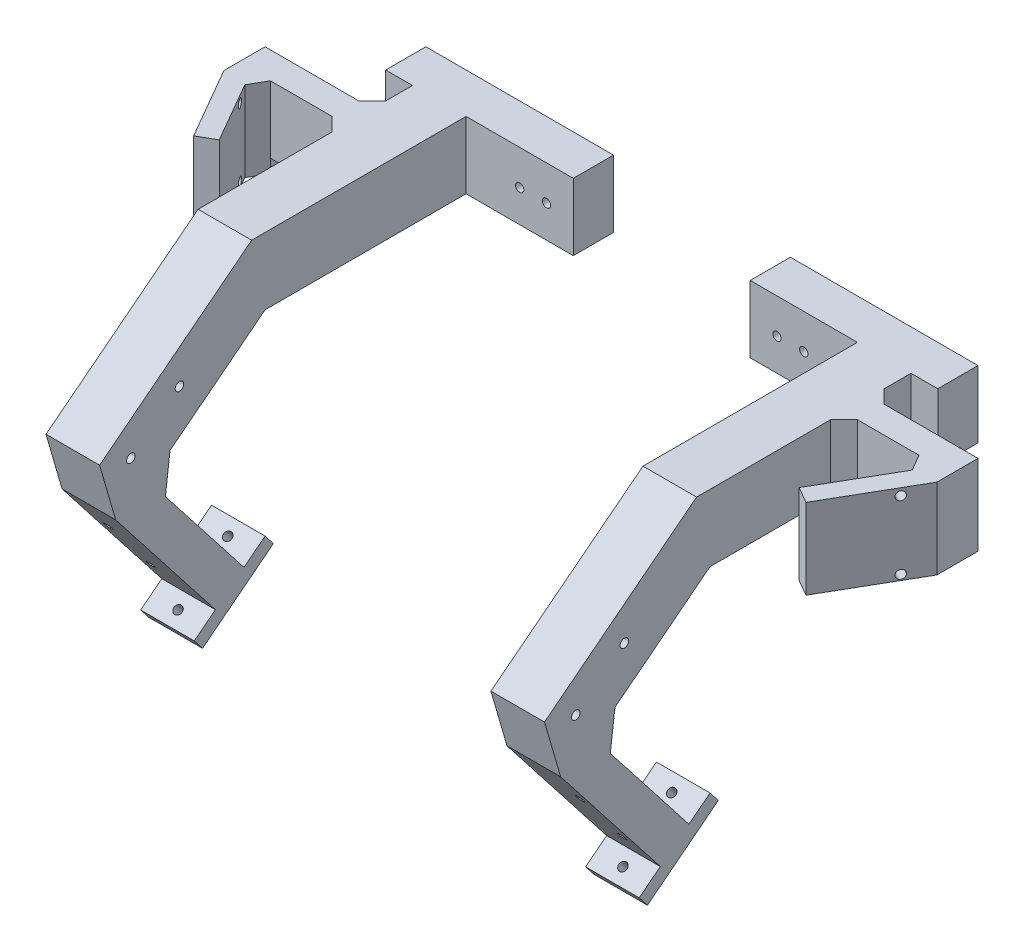
SolidWorks part; units mm, degrees
ref_plane "前视基准面" through (0, 0, 0) normal (0, 0, 1) x (1, 0, 0)
ref_plane "上视基准面" through (0, 0, 0) normal (0, 1, 0) x (1, 0, 0)
ref_plane "右视基准面" through (0, 0, 0) normal (1, 0, 0) x (0, 0, -1)
other "Configuration Table"
sketch "草图1" plane through (0, 0, 0) normal (0, 0, 1) x (1, 0, 0)
  line L1 (-103, 12.5) -> (103, 12.5)
  line L2 (-103, 12.5) -> (-103, -12.5)
  line L3 (-103, -12.5) -> (103, -12.5)
  line L4 (103, 12.5) -> (103, -12.5)
  line L5 (0, -12.5) -> (0, 12.5) construction
  line L6 (-103, 0) -> (103, 0) construction
  point P0 (0, 0)
  dimension "D1" = 25
  dimension "D2" = 206
extrude "凸台-拉伸1" add sketch "草图1" along normal blind 15
sketch "草图3" plane through (103, 0, 0) normal (1, 0, 0) x (0, 0, -1)
  line L2 (-90, -12.5) -> (-133.3406, -46.3614)
  line L6 (-15, 12.5) -> (-15, -12.5)
  line L7 (-15, 12.5) -> (-95, 12.5)
  line L8 (-15, -12.5) -> (-90, -12.5)
  line L13 (-95, 12.5) -> (-158.0409, -36.7529)
  line L14 (-115.7557, -160.3241) -> (-65.323, -120.9218) construction
  line L15 (-158.0409, -36.7529) -> (-133.3406, -46.3614)
  dimension "D1" = 80
  dimension "D2" = 75
  dimension "D3" = 80
  dimension "D4" = 55
extrude "凸台-拉伸2" add sketch "草图3" against normal blind 30
sketch "草图4" plane through (-103, 0, 0) normal (-1, 0, 0) x (0, 0, 1)
  line L6 (15, 12.5) -> (15, -12.5)
  line L7 (15, -12.5) -> (90, -12.5)
  line L8 (90, -12.5) -> (133.3406, -46.3614)
  line L9 (90, -12.5) -> (133.3406, -46.3614)
  line L10 (133.3406, -46.3614) -> (158.0409, -36.7529)
  line L11 (95, 12.5) -> (15, 12.5)
  line L12 (15, 12.5) -> (15, -12.5)
  line L13 (15, -12.5) -> (90, -12.5)
  line L17 (95, 12.5) -> (15, 12.5)
  line L18 (133.3406, -46.3614) -> (158.0409, -36.7529)
  line L19 (158.0409, -36.7529) -> (95, 12.5)
  line L20 (158.0409, -36.7529) -> (95, 12.5)
  dimension "D1" = 0
extrude "凸台-拉伸3" add sketch "草图4" against normal blind 30
extrude "切除-拉伸1" cut sketch "草图3<2>" against normal blind 10
sketch "草图3<2>" plane through (103, 0, 0) normal (1, 0, 0) x (0, 0, -1) same geometry as "草图3"
extrude "切除-拉伸2" cut sketch "草图4<2>" against normal blind 10
sketch "草图4<2>" plane through (-103, 0, 0) normal (-1, 0, 0) x (0, 0, 1) same geometry as "草图4"
sketch "草图12" plane through (0, 0, 15) normal (0, 0, 1) x (1, 0, 0)
  line L1 (73, 12.5) -> (-73, 12.5) construction
  line L2 (-73, 12.5) -> (-73, -12.5) construction
  circle A0 centre (-53, -0.5) radius 1.55
  circle A1 centre (-43, -0.5) radius 1.55
  dimension "D1" = 3.1
  dimension "D4" = 3.1
  dimension "D2" = 20
  dimension "D3" = 13
extrude "切除-拉伸6" cut sketch "草图12" against normal through all
sketch "草图13" plane through (-93, 0, 0) normal (-1, 0, 0) x (0, 0, 1)
  line L0 (133.3406, -46.3614) -> (94.7816, -95.7147)
  line L2 (158.0409, -36.7529) -> (105.4579, -104.056)
  line L3 (158.0409, -36.7529) -> (133.3406, -46.3614)
  line L4 (94.7816, -95.7147) -> (105.4579, -104.056)
extrude "凸台-拉伸5" add sketch "草图13" along direction (-1, 0, 0) on the side against the normal blind 20
sketch "草图14" plane through (93, 0, 0) normal (1, 0, 0) x (0, 0, -1)
  line L4 (-94.7816, -95.7147) -> (-133.3406, -46.3614)
  line L5 (-105.4579, -104.056) -> (-94.7816, -95.7147)
  line L6 (-158.0409, -36.7529) -> (-105.4579, -104.056)
  line L7 (-133.3406, -46.3614) -> (-158.0409, -36.7529)
  line L8 (-94.7816, -95.7147) -> (-133.3406, -46.3614)
  line L9 (-105.4579, -104.056) -> (-94.7816, -95.7147)
  line L10 (-158.0409, -36.7529) -> (-105.4579, -104.056)
  line L11 (-133.3406, -46.3614) -> (-158.0409, -36.7529)
  dimension "D1" = 0
extrude "凸台-拉伸6" add sketch "草图14" against normal blind 20
sketch "草图15" plane through (-93, 0, 0) normal (-1, 0, 0) x (0, 0, 1)
  line L0 (97.8599, -91.7746) -> (89.9798, -85.618)
  line L1 (133.3406, -46.3614) -> (94.7816, -95.7147) construction
  line L2 (97.8599, -91.7746) -> (94.7816, -95.7147)
  line L3 (89.9798, -85.618) -> (86.9015, -89.5581)
  line L5 (86.9015, -89.5581) -> (94.7816, -95.7147)
  line L6 (108.5363, -100.1159) -> (116.4164, -106.2725)
  line L7 (105.4579, -104.056) -> (158.0409, -36.7529) construction
  line L8 (116.4164, -106.2725) -> (113.3381, -110.2126)
  line L9 (113.3381, -110.2126) -> (105.4579, -104.056)
  line L10 (105.4579, -104.056) -> (108.5363, -100.1159)
  dimension "D1" = 10
  dimension "D2" = 5
  dimension "D3" = 10
  dimension "D4" = 5
extrude "凸台-拉伸7" add sketch "草图15" against normal blind 20
sketch "草图16" plane through (93, 0, 0) normal (1, 0, 0) x (0, 0, -1)
  line L4 (-108.5363, -100.1159) -> (-116.4164, -106.2725)
  line L5 (-116.4164, -106.2725) -> (-113.3381, -110.2126)
  line L6 (-113.3381, -110.2126) -> (-105.4579, -104.056)
  line L7 (-105.4579, -104.056) -> (-108.5363, -100.1159)
  line L8 (-108.5363, -100.1159) -> (-116.4164, -106.2725)
  line L9 (-116.4164, -106.2725) -> (-113.3381, -110.2126)
  line L10 (-113.3381, -110.2126) -> (-105.4579, -104.056)
  line L11 (-105.4579, -104.056) -> (-108.5363, -100.1159)
  line L12 (-89.9798, -85.618) -> (-97.8599, -91.7746)
  line L13 (-86.9015, -89.5581) -> (-89.9798, -85.618)
  line L14 (-94.7816, -95.7147) -> (-86.9015, -89.5581)
  line L15 (-97.8599, -91.7746) -> (-94.7816, -95.7147)
  line L16 (-89.9798, -85.618) -> (-97.8599, -91.7746)
  line L17 (-86.9015, -89.5581) -> (-89.9798, -85.618)
  line L18 (-94.7816, -95.7147) -> (-86.9015, -89.5581)
  line L19 (-97.8599, -91.7746) -> (-94.7816, -95.7147)
  dimension "D1" = 0
  dimension "D2" = 0
extrude "凸台-拉伸8" add sketch "草图16" against normal blind 20
sketch "草图17" plane through (0, -9.5119, -7.4315) normal (0, 0.788, 0.6157) x (1, 0, 0)
  circle A0 centre (-83, -152.1653) radius 1.55
  circle A1 centre (-83, -128.6167) radius 1.55
  dimension "D1" = 3.1
  dimension "D2" = 3.1
extrude "切除-拉伸7" cut sketch "草图17" against normal blind 20
sketch "草图20" plane through (0, -9.5119, -7.4315) normal (0, 0.788, 0.6157) x (1, 0, 0)
  circle A0 centre (83, -152.1653) radius 1.55
  circle A1 centre (82.648, -128.6167) radius 1.55
  dimension "D1" = 3.1
  dimension "D2" = 3.1
extrude "切除-拉伸8" cut sketch "草图20" against normal blind 20
sketch "草图21" plane through (0, 0, 0) normal (0, 0, -1) x (-1, 0, 0)
  circle A0 centre (-43, -0.5) radius 1.55
  circle A1 centre (-53, -0.5) radius 1.55
extrude "切除-拉伸9" cut sketch "草图21" against normal blind 20
sketch "草图22" plane through (73, 0, 0) normal (-1, 0, 0) x (0, 0, 1)
  circle A0 centre (140.0641, -35.3981) radius 1.6
  circle A1 centre (121.9398, -21.2379) radius 1.6
extrude "切除-拉伸10" cut sketch "草图22" against normal through all
sketch "草图23" plane through (-73, 0, 0) normal (1, 0, 0) x (0, 0, -1)
  circle A0 centre (-121.9398, -21.2379) radius 1.6
  circle A1 centre (-140.0641, -35.3981) radius 1.6
extrude "切除-拉伸11" cut sketch "草图23" against normal through all
sketch "草图24" plane through (0, -90.604, 115.9678) normal (0, -0.6157, 0.788) x (1, 0, 0)
  line L0 (93, 68.338) -> (93, -12.0708) construction
  line L1 (73, -12.0708) -> (93, -12.0708) construction
  circle A0 centre (88, 28.3292) radius 1.55
  circle A1 centre (88, 2.9292) radius 1.55
  dimension "D3" = 3.1
  dimension "D4" = 3.1
  dimension "D1" = 5
  dimension "D2" = 5
  dimension "D5" = 25.4
  dimension "D6" = 15
extrude "切除-拉伸12" cut sketch "草图24" against normal up to next
sketch "草图25" plane through (0, -90.604, 115.9678) normal (0, -0.6157, 0.788) x (1, 0, 0)
  line L0 (-93, -12.0708) -> (-93, 68.338) construction
  line L1 (-93, 19.0851) -> (-93, -0.6152) construction
  line L2 (-73, -12.0708) -> (-93, -12.0708) construction
  circle A0 centre (-88, 28.3292) radius 1.55
  circle A1 centre (-88, 2.9292) radius 1.55
  dimension "D2" = 3.1
  dimension "D3" = 3.1
  dimension "D1" = 25.4
  dimension "D4" = 5
  dimension "D5" = 5
  dimension "D6" = 15
extrude "切除-拉伸13" cut sketch "草图25" against normal up to next
sketch "草图26" plane through (0, 12.5, 0) normal (0, 1, 0) x (1, 0, 0)
  line L0 (-93, -30) -> (-93, -40)
  line L1 (-93, -95) -> (-93, -15) construction
  line L2 (-93, -40) -> (-128, -40)
  line L3 (-133, -45.3397) -> (-133, -30)
  line L4 (-133, -30) -> (-93, -30)
  line L5 (-128, -40) -> (-111.478, -68.617)
  line L6 (-111.478, -68.617) -> (-117.5401, -72.117)
  line L7 (-117.5401, -72.117) -> (-133, -45.3397)
  line L8 (-93, -15) -> (-103, -15) construction
  dimension "D1" = 15
  dimension "D2" = 10
  dimension "D3" = 60
  dimension "D4" = 40
  dimension "D5" = 35
  dimension "D7" = 7
extrude "凸台-拉伸9" add sketch "草图26" along direction (0, 1, 0) on the side against the normal blind 25
sketch "草图27" plane through (0, -12.5, 0) normal (0, -1, 0) x (1, 0, 0)
  line L0 (93, 30) -> (133, 30)
  line L1 (93, 90) -> (93, 15) construction
  line L2 (133, 30) -> (133, 45.3397)
  line L3 (128, 40) -> (93, 40)
  line L4 (93, 40) -> (93, 30)
  line L5 (133, 45.3397) -> (115.124, 76.3019)
  line L6 (115.124, 76.3019) -> (109.0618, 72.8019)
  line L7 (109.0618, 72.8019) -> (128, 40)
  line L8 (93, 15) -> (103, 15) construction
  dimension "D1" = 7
  dimension "D2" = 40
  dimension "D3" = 15
  dimension "D5" = 35
  dimension "D6" = 60
  dimension "D8" = 10
extrude "凸台-拉伸10" add sketch "草图27" against normal blind 25
sketch "草图28" plane through (0, 12.5, 0) normal (0, 1, 0) x (1, 0, 0)
  line L0 (-124.5, -46.0622) -> (-121, -40)
  line L1 (-111.478, -68.617) -> (-128, -40) construction
  line L2 (-128, -40) -> (-93, -40) construction
  line L3 (-121, -40) -> (-128, -40)
  line L4 (-128, -40) -> (-124.5, -46.0622)
  line L5 (121, -40) -> (128, -40)
  line L6 (128, -40) -> (93, -40) construction
  line L7 (128, -40) -> (124.5, -46.0622)
  line L8 (109.0618, -72.8019) -> (128, -40) construction
  line L9 (124.5, -46.0622) -> (121, -40)
  dimension "D1" = 7
  dimension "D2" = 7
  dimension "D3" = 7
  dimension "D4" = 7
extrude "凸台-拉伸11" add sketch "草图28" against normal blind 25
sketch "草图29" plane through (0, 12.5, 0) normal (0, 1, 0) x (1, 0, 0)
  line L0 (-124.5, -46.0622) -> (-111.478, -68.617)
  line L1 (-111.478, -68.617) -> (-117.5401, -72.117)
  line L2 (-117.5401, -72.117) -> (-133, -45.3397)
  line L3 (-133, -45.3397) -> (-117.5401, -72.117) construction
  line L4 (-133, -45.3397) -> (-133, -30)
  line L5 (-133, -30) -> (-121, -30)
  line L6 (-93, -30) -> (-133, -30) construction
  line L7 (-121, -30) -> (-121, -40)
  line L8 (-121, -40) -> (-124.5, -46.0622)
  line L9 (109.0618, -72.8019) -> (115.124, -76.3019)
  line L10 (115.124, -76.3019) -> (133, -45.3397)
  line L11 (133, -45.3397) -> (133, -30)
  line L12 (109.0618, -72.8019) -> (124.5, -46.0622)
  line L13 (124.5, -46.0622) -> (121, -40)
  line L14 (121, -40) -> (121, -30)
  line L15 (93, -30) -> (133, -30) construction
  line L16 (121, -30) -> (133, -30)
sketch "草图30" plane through (0, -12.5, 0) normal (0, -1, 0) x (1, 0, 0)
  line L7 (-124.5, 46.0622) -> (-111.478, 68.617)
  line L8 (-111.478, 68.617) -> (-117.5401, 72.117)
  line L9 (-117.5401, 72.117) -> (-133, 45.3397)
  line L10 (-133, 45.3397) -> (-133, 30)
  line L11 (-133, 30) -> (-121, 30)
  line L12 (-121, 30) -> (-121, 40)
  line L13 (-121, 40) -> (-124.5, 46.0622)
  line L14 (-124.5, 46.0622) -> (-111.478, 68.617)
  line L15 (-111.478, 68.617) -> (-117.5401, 72.117)
  line L16 (-117.5401, 72.117) -> (-133, 45.3397)
  line L17 (-133, 45.3397) -> (-133, 30)
  line L18 (-133, 30) -> (-121, 30)
  line L19 (-121, 30) -> (-121, 40)
  line L20 (-121, 40) -> (-124.5, 46.0622)
  line L21 (133, 45.3397) -> (115.124, 76.3019)
  line L22 (133, 30) -> (133, 45.3397)
  line L23 (121, 30) -> (133, 30)
  line L24 (121, 40) -> (121, 30)
  line L25 (124.5, 46.0622) -> (121, 40)
  line L26 (109.0618, 72.8019) -> (124.5, 46.0622)
  line L27 (115.124, 76.3019) -> (109.0618, 72.8019)
  line L28 (133, 45.3397) -> (115.124, 76.3019)
  line L29 (133, 30) -> (133, 45.3397)
  line L30 (121, 30) -> (133, 30)
  line L31 (121, 40) -> (121, 30)
  line L32 (124.5, 46.0622) -> (121, 40)
  line L33 (109.0618, 72.8019) -> (124.5, 46.0622)
  line L34 (115.124, 76.3019) -> (109.0618, 72.8019)
  dimension "D1" = 0
  dimension "D2" = 0
extrude "凸台-拉伸13" add sketch "草图30" along normal blind 5
sketch "草图31" plane through (119.3827, 0, 68.9256) normal (0.866, 0, 0.5) x (0.5, 0, -0.866)
  line L1 (27.2346, -17.5) -> (-8.5174, -17.5) construction
  circle A0 centre (17.359, 9.9) radius 1.6
  circle A1 centre (17.359, -15.5) radius 1.6
  dimension "D5" = 3.2
  dimension "D6" = 3.2
  dimension "D2" = 0
  dimension "D3" = 25.4
  dimension "D4" = 2
extrude "切除-拉伸14" cut sketch "草图31" against normal up to next and the other way through all
sketch "草图33" plane through (-119.3827, 0, 68.9256) normal (-0.866, 0, 0.5) x (0.5, 0, 0.866)
  line L0 (3.6851, -17.5) -> (-27.2346, -17.5) construction
  circle A0 centre (-17.359, 9.9) radius 1.6
  circle A1 centre (-17.359, -15.5) radius 1.6
  dimension "D5" = 3.2
  dimension "D6" = 3.2
  dimension "D2" = 25.4
  dimension "D3" = 2
  dimension "D4" = 0
extrude "切除-拉伸15" cut sketch "草图33" against normal up to next
sketch "草图34" plane through (0, 12.5, 0) normal (0, 1, 0) x (1, 0, 0)
  line L0 (-98, -40) -> (-93, -45)
  line L1 (-121, -40) -> (-93, -40) construction
  line L2 (-93, -95) -> (-93, -40) construction
  line L3 (-93, -40) -> (-93, -45)
  line L4 (-98, -40) -> (-93, -40)
  line L5 (-98, -30) -> (-93, -25)
  line L6 (-93, -30) -> (-133, -30) construction
  line L7 (-93, -30) -> (-93, -15) construction
  line L8 (-93, -25) -> (-93, -30)
  line L9 (-93, -30) -> (-98, -30)
  line L20 (93, -25) -> (93, -30)
  line L21 (93, -15) -> (93, -30) construction
  line L22 (93, -30) -> (98, -30)
  line L23 (93, -30) -> (133, -30) construction
  line L24 (98, -30) -> (93, -25)
  line L25 (93, -45) -> (93, -40)
  line L26 (93, -40) -> (93, -95) construction
  line L27 (93, -40) -> (98, -40)
  line L28 (98, -40) -> (93, -45)
  dimension "D1" = 5
  dimension "D2" = 5
  dimension "D3" = 5
  dimension "D4" = 5
  dimension "D5" = 5
  dimension "D6" = 5
  dimension "D7" = 5
extrude "凸台-拉伸14" add sketch "草图34" along direction (0, 1, 0) on the side against the normal blind 25
sketch "草图35" plane through (-93, 0, 0) normal (-1, 0, 0) x (0, 0, 1)
  line L0 (125.4605, -40.2048) -> (133.3406, -46.3614)
  line L1 (90, -12.5) -> (133.3406, -46.3614) construction
  line L2 (133.3406, -46.3614) -> (127.184, -54.2415)
  line L3 (133.3406, -46.3614) -> (97.8599, -91.7746) construction
  line L4 (127.184, -54.2415) -> (125.4605, -40.2048)
  dimension "D1" = 10
  dimension "D2" = 10
extrude "凸台-拉伸15" add sketch "草图35" against normal blind 20
sketch "草图36" plane through (93, 0, 0) normal (1, 0, 0) x (0, 0, -1)
  line L0 (-125.4605, -40.2048) -> (-133.3406, -46.3614)
  line L1 (-133.3406, -46.3614) -> (-127.184, -54.2415)
  line L2 (-127.184, -54.2415) -> (-125.4605, -40.2048)
extrude "凸台-拉伸16" add sketch "草图36" against normal blind 20
sketch "草图37" plane through (-93, 0, 0) normal (-1, 0, 0) x (0, 0, 1)
  line L0 (145.7276, -52.5131) -> (151.7368, -31.8276)
  line L1 (108.5363, -100.1159) -> (158.0409, -36.7529) construction
  line L2 (151.7368, -31.8276) -> (158.0409, -36.7529)
  line L3 (158.0409, -36.7529) -> (145.7276, -52.5131)
  line L4 (158.0409, -36.7529) -> (95, 12.5) construction
  dimension "D1" = 8
  dimension "D2" = 20
extrude "切除-拉伸16" cut sketch "草图37" against normal through all
sketch "草图38" plane through (0, 0, 15) normal (0, 0, 1) x (1, 0, 0)
  line L0 (73, 12.5) -> (-73, 12.5) construction
  line L1 (-33, 12.5) -> (33, 12.5)
  line L2 (-33, 12.5) -> (-33, -12.5)
  line L3 (-33, -12.5) -> (33, -12.5)
  line L4 (33, 12.5) -> (33, -12.5)
  line L5 (-73, -12.5) -> (73, -12.5) construction
  line L6 (-73, 12.5) -> (-73, -12.5) construction
  line L7 (73, -12.5) -> (73, 12.5) construction
  dimension "D1" = 40
  dimension "D2" = 40
extrude "切除-拉伸17" cut sketch "草图38" against normal through all
